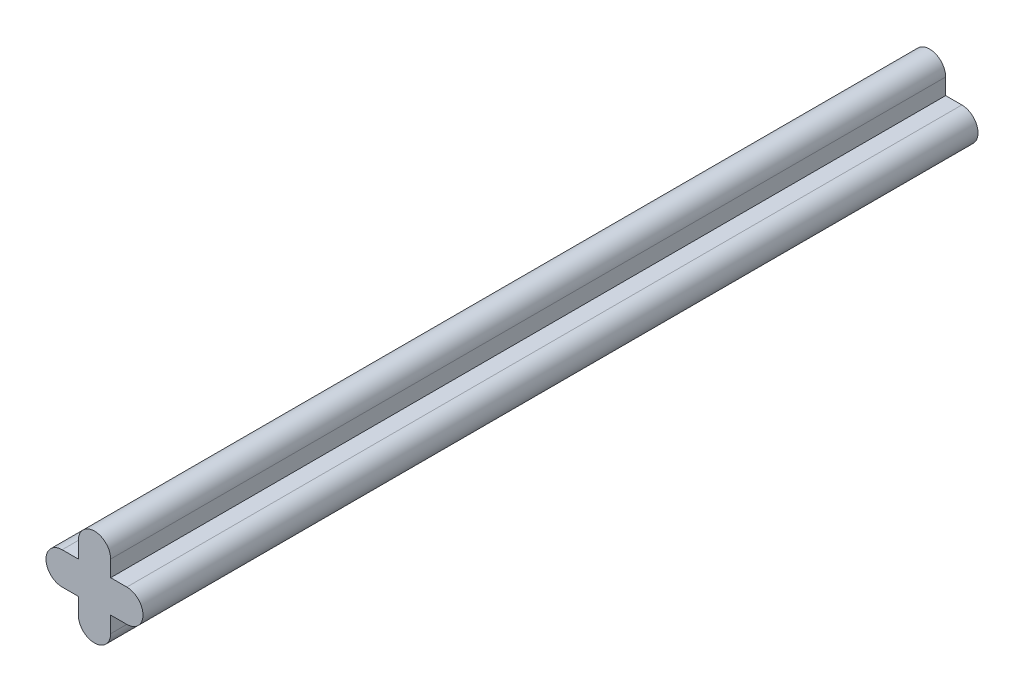
SolidWorks part; units mm, degrees
material "PVC Rigid"
ref_plane "Front Plane" through (0, 0, 0) normal (0, 0, 1) x (1, 0, 0)
ref_plane "Top Plane" through (0, 0, 0) normal (0, 1, 0) x (1, 0, 0)
ref_plane "Right Plane" through (0, 0, 0) normal (1, 0, 0) x (0, 0, -1)
sketch "Sketch1" plane through (0, 0, 0) normal (0, 0, 1) x (1, 0, 0)
  line L0 (0, 0) -> (3.048, 0) construction
  line L1 (0, 0.762) -> (3.048, 0.762)
  line L2 (0, -0.762) -> (3.048, -0.762)
  line L8 (1.524, 1.524) -> (1.524, -1.524) construction
  line L9 (2.286, 1.524) -> (2.286, -1.524)
  line L10 (0.762, 1.524) -> (0.762, -1.524)
  arc A0 (0, 0.762) -> (0, -0.762) centre (0, 0) ccw
  arc A2 (3.048, -0.762) -> (3.048, 0.762) centre (3.048, 0) ccw
  arc A4 (2.286, 1.524) -> (0.762, 1.524) centre (1.524, 1.524) ccw
  arc A5 (0.762, -1.524) -> (2.286, -1.524) centre (1.524, -1.524) ccw
  circle A7 centre (1.524, 0) radius 2.286 construction
  point P1 (3.81, 0)
  point P3 (1.524, 0)
  point P8 (1.524, 0)
  point P13 (5.334, 0)
  point P15 (7.62, 0)
  point P17 (0, 3.302)
  point P18 (19.05, 3.302)
  point P19 (0, -3.302)
  point P20 (19.05, -3.302)
  point P23 (13.843, 0)
  point P24 (3.81, 0)
  point P25 (23.368, 0)
  point P26 (3.429, 0)
  point P27 (-7.874, -3.302)
  point P28 (7.874, -3.302)
  point P29 (-7.874, 3.302)
  point P30 (7.874, 3.302)
  point P35 (11.811, 0)
  point P60 (11.5175, 1.1139)
  dimension "D2" = 1.524
  dimension "D3" = 4.572
  dimension "D1" = 1.524
extrude "Boss-Extrude1" add sketch "Sketch1" along normal blind 39.37 contours L1 A0 L2 L10 | L9 A4 L10 L1 | L2 A2 L1 L9 | L10 A5 L9 L2 | L1 L10 L2 L9 region at (0.0711, 0, 0) region at (1.524, 1.4529, 0) region at (1.524, 0, 0) region at (2.9769, 0, 0) region at (1.524, -1.4529, 0)
sketch "Sketch2" plane through (0, 0, 0) normal (0, 0, -1) x (-1, 0, 0)
  circle A0 centre (-1.524, 0) radius 2.286
sketch "Sketch3" plane through (0, 0, 39.37) normal (0, 0, 1) x (1, 0, 0)
  circle A0 centre (1.524, 0) radius 2.286 construction
  circle A1 centre (1.524, 0) radius 2.286
ref_plane "Plane1" through (0, 0, 19.685) normal (0, 0, -1) x (-1, 0, 0)
sketch "Sketch4" plane through (0, 0, 19.685) normal (0, 0, -1) x (-1, 0, 0)
  circle A0 centre (-1.524, 0) radius 2.286 construction
  circle A1 centre (-1.524, 0) radius 2.286
